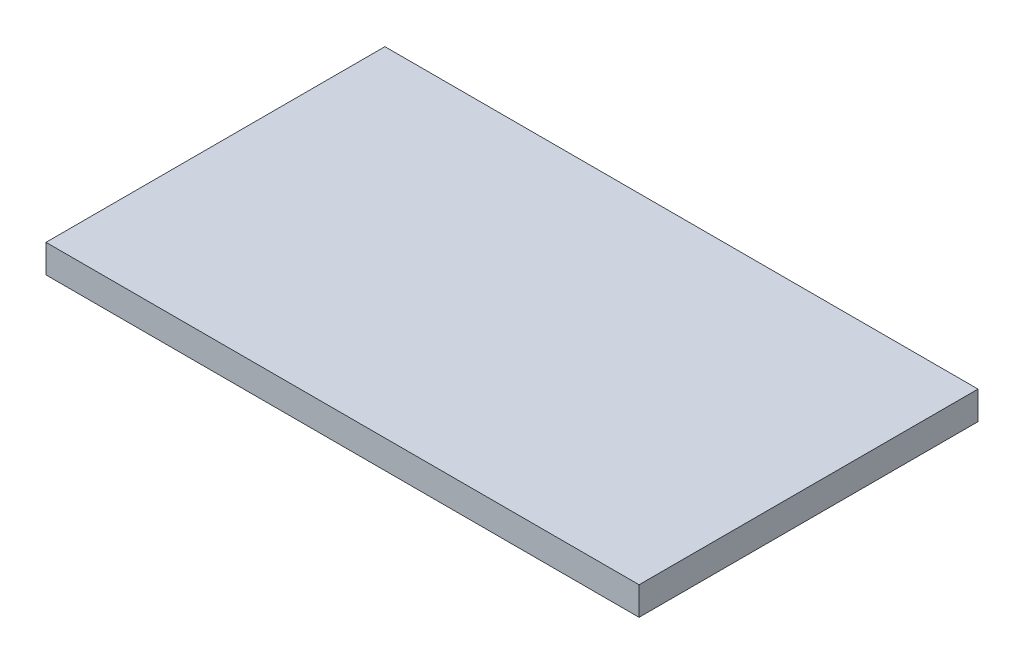
SolidWorks part; units mm, degrees
ref_plane "Front Plane" through (0, 0, 0) normal (0, 0, 1) x (1, 0, 0)
ref_plane "Top Plane" through (0, 0, 0) normal (0, 1, 0) x (1, 0, 0)
ref_plane "Right Plane" through (0, 0, 0) normal (1, 0, 0) x (0, 0, -1)
sketch "Sketch1" plane through (0, 0, 0) normal (0, 1, 0) x (1, 0, 0)
  line L1 (0, 0) -> (210, 0)
  line L2 (0, 0) -> (0, 120)
  line L3 (0, 120) -> (210, 120)
  line L4 (210, 0) -> (210, 120)
  dimension "D1" = 210
  dimension "D2" = 120
extrude "Boss-Extrude1" add sketch "Sketch1" along normal blind 10
